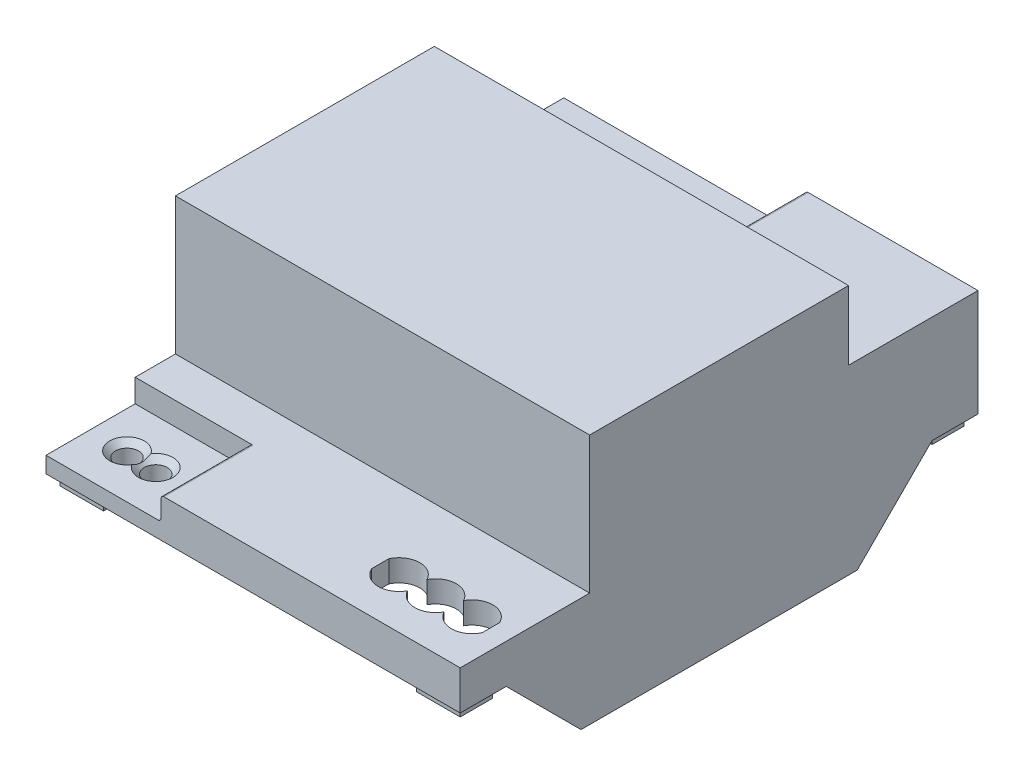
SolidWorks part; units mm, degrees
ref_plane "前视基准面" through (0, 0, 0) normal (0, 0, 1) x (1, 0, 0)
ref_plane "上视基准面" through (0, 0, 0) normal (0, 1, 0) x (1, 0, 0)
ref_plane "右视基准面" through (0, 0, 0) normal (1, 0, 0) x (0, 0, -1)
other "Configuration Table"
sketch "草图1" plane through (0, 0, 0) normal (0, 1, 0) x (1, 0, 0)
  line L1 (-36, 45) -> (36, 45)
  line L2 (-36, 45) -> (-36, -45)
  line L3 (-36, -45) -> (36, -45)
  line L4 (36, 45) -> (36, -45)
  dimension "D1" = 72
  dimension "D2" = 90
  dimension "D3" = 36
  dimension "D4" = 45
extrude "凸台-拉伸1" add sketch "草图1" along normal blind 43.6
sketch "草图2" plane through (36, 0, 0) normal (1, 0, 0) x (0, 0, -1)
  line L0 (-45, 0) -> (-45, 13)
  line L1 (-45, 43.6) -> (-45, 0) construction
  line L3 (-45, 0) -> (45, 0) construction
  line L4 (-24, 0) -> (-45, 0)
  line L5 (-45, 13) -> (-37, 13)
  line L6 (-37, 13) -> (-24, 0)
  dimension "D1" = 8
  dimension "D2" = 21
  dimension "D3" = 13
ref_plane "基准面1" through (0, 0, 0) normal (0, 0, -1) x (-1, 0, 0)
extrude "切除-拉伸1" cut sketch "草图2" against normal blind 72
mirror "镜向1" about plane through (0, 0, 0) normal (0, 0, -1) of "切除-拉伸1"
sketch "草图3" plane through (36, 0, 0) normal (1, 0, 0) x (0, 0, -1)
  line L0 (0, -16.83) -> (0, 16.83) construction
  line L1 (-45, 43.6) -> (-22.5, 43.6)
  line L2 (-45, 43.6) -> (-45, 19.8)
  line L3 (-45, 19.8) -> (-22.5, 19.8)
  line L4 (-22.5, 43.6) -> (-22.5, 19.8)
  line L5 (-37, 13) -> (-45, 13) construction
  dimension "D1" = 22.5
  dimension "D2" = 6.8
extrude "切除-拉伸2" cut sketch "草图3" against normal blind 72
sketch "草图5" plane through (0, 0, 0) normal (0, -1, 0) x (1, 0, 0)
  line L84 (-34, 20.5) -> (34, 20.5)
  line L85 (-10.23, 0) -> (10.23, 0) construction
  line L94 (34, 43) -> (-34, 43)
  line L95 (34, 37) -> (34, 43)
  line L96 (34, 24) -> (34, 37)
  line L97 (34, -24) -> (34, 24)
  line L98 (34, -37) -> (34, -24)
  line L99 (34, -43) -> (34, -37)
  line L100 (-34, -43) -> (34, -43)
  line L101 (-34, -37) -> (-34, -43)
  line L102 (-34, -24) -> (-34, -37)
  line L103 (-34, 43) -> (-34, 37)
  line L104 (-34, 37) -> (-34, 24)
  line L105 (-34, 24) -> (-34, -24)
  line L106 (34, 43) -> (-34, 43)
  line L107 (34, 37) -> (34, 43)
  line L108 (34, 20.5) -> (34, 37)
  line L115 (-34, 43) -> (-34, 37)
  line L116 (-34, 37) -> (-34, 20.5)
  dimension "D2" = 20.5
  dimension "D1" = 2
extrude "切除-拉伸4" cut sketch "草图5" against normal blind 16
sketch "草图6" plane through (0, 0, 0) normal (0, -1, 0) x (1, 0, 0)
  line L1 (-34, 20.5) -> (34, 20.5)
  line L2 (-34, 20.5) -> (-34, -20.5)
  line L3 (-34, -20.5) -> (34, -20.5)
  line L4 (34, 20.5) -> (34, -20.5)
  line L6 (-10.23, 0) -> (10.23, 0) construction
  line L7 (36, 24) -> (36, -24) construction
  line L8 (-36, -24) -> (-36, 24) construction
  dimension "D1" = 41
  dimension "D2" = 20.5
  dimension "D3" = 2
  dimension "D4" = 2
extrude "切除-拉伸5" cut sketch "草图6" against normal blind 42
sketch "草图7" plane through (0, 13, 0) normal (0, -1, 0) x (1, 0, 0)
  line L0 (-34, 38.2) -> (-34.8, 38.2)
  line L1 (-34, 43) -> (-34, 20.5) construction
  line L2 (-34.8, 38.2) -> (-34.8, 43.8)
  line L3 (-34.8, 43.8) -> (-27.2, 43.8)
  line L4 (-27.2, 43.8) -> (-27.2, 43)
  line L5 (-27.2, 43) -> (-34, 43)
  line L6 (-34, 43) -> (-34, 38.2)
  line L7 (-34, 43) -> (34, 43) construction
  line L8 (-36, 37) -> (-36, 45) construction
  line L9 (-36, 45) -> (36, 45) construction
  dimension "D1" = 1.2
  dimension "D2" = 1.2
  dimension "D3" = 4.8
  dimension "D4" = 6.8
extrude "凸台-拉伸2" add sketch "草图7" along normal blind 1.8
mirror "镜向4" about plane through (0, 0, 0) normal (1, 0, 0) of "凸台-拉伸2"
mirror "镜向5" about plane through (0, 0, 0) normal (0, 0, 1) of "镜向4"
sketch "草图8" plane through (0, 19.8, 0) normal (0, 1, 0) x (1, 0, 0)
  line L0 (36, -45) -> (36, -22.5) construction
  line L2 (32.62, -37.7748) -> (32.62, -34.7852)
  line L4 (13.37, -37.7748) -> (13.37, -34.7852)
  line L5 (-36, -45) -> (36, -45) construction
  arc A0 (13.37, -37.7748) -> (19.82, -37.9769) centre (16.645, -36.28) ccw
  arc A1 (19.82, -37.9769) -> (26.17, -37.9769) centre (22.995, -36.28) ccw
  arc A2 (32.62, -34.7852) -> (26.17, -34.5831) centre (29.345, -36.28) ccw
  arc A3 (19.82, -34.5831) -> (13.37, -34.7852) centre (16.645, -36.28) ccw
  arc A4 (26.17, -34.5831) -> (19.82, -34.5831) centre (22.995, -36.28) ccw
  arc A5 (26.17, -37.9769) -> (32.62, -37.7748) centre (29.345, -36.28) ccw
  dimension "D2" = 3.6
  dimension "D3" = 3.6
  dimension "D7" = 3.6
  dimension "D1" = 3.38
  dimension "D4" = 6.35
  dimension "D5" = 6.35
  dimension "D6" = 3.275
  dimension "D8" = 19.25
  dimension "D9" = 8.72
extrude "切除-拉伸6" cut sketch "草图8" against normal blind 3.8
sketch "草图10" plane through (0, 16, 0) normal (0, -1, 0) x (1, 0, 0)
  line L0 (34, 20.5) -> (-34, 20.5) construction
  line L1 (-34, 43) -> (-14, 43)
  line L2 (-34, 43) -> (-34, 20.5)
  line L3 (-34, 20.5) -> (-14, 20.5)
  line L4 (-14, 43) -> (-14, 20.5)
  dimension "D2" = 20
extrude "凸台-拉伸3" add sketch "草图10" along normal blind 4
sketch "草图9" plane through (-36, 0, 0) normal (-1, 0, 0) x (0, 0, 1)
  line L0 (45, 19.8) -> (22.5, 19.8) construction
  line L1 (45, 19.8) -> (29.5, 19.8)
  line L2 (45, 19.8) -> (45, 15.8)
  line L3 (45, 15.8) -> (29.5, 15.8)
  line L4 (29.5, 19.8) -> (29.5, 15.8)
  line L5 (45, 19.8) -> (45, 13) construction
  line L7 (22.5, 19.8) -> (22.5, 43.6) construction
  dimension "D1" = 7
  dimension "D2" = 4
extrude "切除-拉伸7" cut sketch "草图9" against normal blind 20
sketch "草图11" plane through (0, 15.8, 0) normal (0, 1, 0) x (1, 0, 0)
  line L0 (-36, -29.5) -> (-36, -45) construction
  line L1 (-16, -45) -> (-36, -45) construction
  circle A0 centre (-29.622, -37.3) radius 2
  circle A1 centre (-24.622, -37.3) radius 2
  dimension "D2" = 4
  dimension "D3" = 4
  dimension "D1" = 5
  dimension "D4" = 6.378
  dimension "D5" = 7.7
extrude "切除-拉伸8" cut sketch "草图11" against normal blind 4
chamfer "倒角1" distance 1 angle 45 2 edges at (-24.622, 15.8, 39.3) (-29.622, 15.8, 39.3)
sketch "草图13" plane through (0, 12, 0) normal (0, -1, 0) x (1, 0, 0)
  line L0 (-34, 24) -> (-34, 36) construction
  line L1 (-14, 20.5) -> (-34, 20.5)
  line L2 (-14, 20.5) -> (-14, 27.5)
  line L3 (-14, 27.5) -> (-34, 27.5)
  line L4 (-34, 20.5) -> (-34, 27.5)
  dimension "D1" = 7
extrude "切除-拉伸10" cut sketch "草图13" against normal blind 1.6
sketch "草图15" plane through (0, 16, 0) normal (0, -1, 0) x (1, 0, 0)
  line L0 (34, 20.5) -> (34, 43) construction
  line L1 (-14, 20.5) -> (34, 20.5)
  line L2 (-14, 20.5) -> (-14, 27.5)
  line L3 (-14, 27.5) -> (34, 27.5)
  line L4 (34, 20.5) -> (34, 27.5)
  line L5 (-14, 27.5) -> (-34, 27.5) construction
extrude "凸台-拉伸4" add sketch "草图15" along normal up to surface (2.4 mm away) up to face at (-24, 13.6, 24)
sketch "草图14" plane through (0, 13.6, 0) normal (0, -1, 0) x (1, 0, 0)
  line L0 (-36, -24) -> (-36, 24) construction
  line L1 (-14, 27.5) -> (-34, 27.5) construction
  line L3 (34, 27.5) -> (-14, 27.5) construction
  circle A0 centre (-26, 24) radius 1.75
  circle A2 centre (-6, 24) radius 1.75
  dimension "D1" = 3.5
  dimension "D5" = 3.5
  dimension "D2" = 10
  dimension "D3" = 3.5
  dimension "D4" = 20
  dimension "D6" = 3.5
extrude "切除-拉伸11" cut sketch "草图14" against normal blind 5
sketch "草图16" plane through (0, 0, 0) normal (0, -1, 0) x (1, 0, 0)
  line L1 (-34, -20.5) -> (34, -20.5)
  line L2 (-34, -20.5) -> (-34, -43)
  line L3 (-34, -43) -> (34, -43)
  line L4 (34, -20.5) -> (34, -43)
extrude "切除-拉伸12" cut sketch "草图16" against normal blind 30
sketch "草图18" plane through (0, 13.6, 0) normal (0, -1, 0) x (1, 0, 0)
  line L3 (5.8, 27.3) -> (5.8, 2)
  line L4 (15.8, -8) -> (33.8, -8)
  line L5 (-36, 45) -> (36, 45) construction
  line L22 (34, 27.3) -> (-14, 27.3)
  line L23 (-14, 27.3) -> (-34, 27.3)
  line L24 (5.8, 27.3) -> (-14, 27.3)
  line L25 (-14, 27.3) -> (-33.8, 27.3)
  line L34 (33.8, -24) -> (33.8, 24)
  line L35 (33.8, -42.8) -> (33.8, -8)
  line L37 (-33.8, 24) -> (-33.8, -24)
  line L38 (-33.8, 27.3) -> (-33.8, -42.8)
  line L40 (-34, -42.8) -> (34, -42.8)
  line L41 (-33.8, -42.8) -> (33.8, -42.8)
  arc A0 (5.8, 2) -> (15.8, -8) centre (15.8, 2) ccw
  dimension "D6" = 10
  dimension "D5" = 53
  dimension "D7" = 28
  dimension "D1" = 0.2
  dimension "D2" = 0.2
  dimension "D3" = 0.2
  dimension "D4" = 0.2
sketch "草图19" plane through (0, 0, -45) normal (0, 0, -1) x (-1, 0, 0)
  line L0 (24.25, 13.6) -> (27.75, 13.6) construction
  line L1 (-27, 27.6) -> (-11, 27.6)
  line L2 (-27, 27.6) -> (-27, 13.6)
  line L3 (-27, 13.6) -> (-11, 13.6)
  line L4 (-11, 27.6) -> (-11, 13.6)
  line L6 (-36, 43.6) -> (-36, 13) construction
  dimension "D1" = 16
  dimension "D2" = 14
  dimension "D3" = 9
extrude "切除-拉伸13" cut sketch "草图19" against normal blind 2
sketch "草图20" plane through (0, 30, 0) normal (0, -1, 0) x (1, 0, 0)
  line L0 (-34, -20.5) -> (-34, -43) construction
  line L3 (-34, -36.8) -> (-27.8, -36.8)
  line L4 (-27.8, -43) -> (-27.8, -36.8)
  line L7 (34, -36.8) -> (27.8, -36.8)
  line L8 (27.8, -43) -> (27.8, -36.8)
  line L9 (-34, -36.8) -> (-34, -43)
  line L10 (-34, -43) -> (-27.8, -43)
  line L11 (-27.2, -43) -> (27.2, -43) construction
  line L14 (34, -43) -> (34, -20.5) construction
  line L15 (34, -43) -> (27.2, -43) construction
  line L16 (-34, -38.2) -> (-34, -43) construction
  line L17 (-34, -43) -> (34, -43) construction
  line L18 (27.8, -43) -> (34, -43)
  line L19 (34, -38.2) -> (34, -43) construction
  line L20 (34, -43) -> (34, -36.8)
  line L21 (34, -37) -> (34, -24) construction
  circle A0 centre (-30.8, -39.8) radius 1.75
  circle A1 centre (30.8, -39.8) radius 1.75
  circle A2 centre (5, -39.8) radius 4
  circle A3 centre (5, -39.8) radius 1.75
  dimension "D5" = 3.5
  dimension "D6" = 3.5
  dimension "D4" = 3.5
  dimension "D9" = 8
  dimension "D2" = 6.2
  dimension "D3" = 6.2
  dimension "D7" = 6.2
  dimension "D8" = 6.2
  dimension "D10" = 5
  dimension "D11" = 30.8
  dimension "D12" = 39.8
  dimension "D13" = 30.8
  dimension "D14" = 39.8
  dimension "D15" = 39.8
extrude "凸台-拉伸5" add sketch "草图20" along normal up to surface (16.4 mm away) up to face at (-26, 13.6, 22.25)
sketch "草图21" plane through (0, 0, -45) normal (0, 0, -1) x (-1, 0, 0)
  line L0 (36, 43.6) -> (36, 13) construction
  line L1 (23.46, 17.5) -> (26.06, 17.5)
  line L2 (23.46, 17.5) -> (23.46, 14.5)
  line L3 (23.46, 14.5) -> (26.06, 14.5)
  line L4 (26.06, 17.5) -> (26.06, 14.5)
  line L5 (19.65, 17.5) -> (22.25, 17.5)
  line L6 (19.65, 17.5) -> (19.65, 14.5)
  line L7 (19.65, 14.5) -> (22.25, 14.5)
  line L8 (22.25, 17.5) -> (22.25, 14.5)
  line L9 (15.84, 17.5) -> (18.44, 17.5)
  line L10 (15.84, 17.5) -> (15.84, 14.5)
  line L11 (15.84, 14.5) -> (18.44, 14.5)
  line L12 (18.44, 17.5) -> (18.44, 14.5)
  line L13 (36, 13) -> (-36, 13) construction
  line L14 (8.46, 17.5) -> (11.06, 17.5)
  line L15 (8.46, 17.5) -> (8.46, 14.5)
  line L16 (8.46, 14.5) -> (11.06, 14.5)
  line L17 (11.06, 17.5) -> (11.06, 14.5)
  line L18 (4.65, 17.5) -> (7.25, 17.5)
  line L19 (4.65, 17.5) -> (4.65, 14.5)
  line L20 (4.65, 14.5) -> (7.25, 14.5)
  line L21 (7.25, 17.5) -> (7.25, 14.5)
  line L22 (0.84, 17.5) -> (3.44, 17.5)
  line L23 (0.84, 17.5) -> (0.84, 14.5)
  line L24 (0.84, 14.5) -> (3.44, 14.5)
  line L25 (3.44, 17.5) -> (3.44, 14.5)
  dimension "D1" = 2.6
  dimension "D2" = 3
  dimension "D3" = 2.6
  dimension "D4" = 2.6
  dimension "D5" = 1.21
  dimension "D6" = 1.21
  dimension "D7" = 9.94
  dimension "D8" = 1.5
  dimension "D9" = 2.6
  dimension "D10" = 3
  dimension "D11" = 2.6
  dimension "D12" = 2.6
  dimension "D13" = 1.21
  dimension "D14" = 1.21
  dimension "D15" = 4.78
extrude "切除-拉伸14" cut sketch "草图21" against normal blind 2
sketch "草图22" plane through (0, 30, 0) normal (0, -1, 0) x (1, 0, 0)
  circle A17 centre (30.8, -39.8) radius 1.75
  circle A18 centre (30.8, -39.8) radius 1.75
  circle A20 centre (5, -39.8) radius 1.75
  circle A21 centre (5, -39.8) radius 1.75
  circle A23 centre (-30.8, -39.8) radius 1.75
  circle A24 centre (-30.8, -39.8) radius 1.75
  dimension "D1" = 0
  dimension "D2" = 0
  dimension "D3" = 0
extrude "凸台-拉伸6" add sketch "草图22" along normal blind 11.4
sketch "草图24" plane through (0, 30, 0) normal (0, -1, 0) x (1, 0, 0)
  line L0 (-34, -20.5) -> (34, -20.5) construction
  line L1 (-34, -43) -> (9, -43)
  line L2 (-34, -43) -> (-34, -20.5)
  line L3 (-34, -20.5) -> (9, -20.5)
  line L4 (9, -43) -> (9, -20.5)
  arc A0 (7.4, -43) -> (2.6, -43) centre (5, -39.8) ccw construction
extrude "凸台-拉伸7" add sketch "草图24" along normal blind 7.5
chamfer "倒角3" distance 0.5 angle 45 24 edges at (-24.76, 14.5, -45) (-23.46, 16, -45) (-26.06, 16, -45) (-24.76, 17.5, -45) (-22.25, 16, -45) (-20.95, 17.5, -45) (-19.65, 16, -45) (-20.95, 14.5, -45) (-17.14, 14.5, -45) (-18.44, 16, -45) (-15.84, 16, -45) (-17.14, 17.5, -45) (-9.76, 14.5, -45) (-8.46, 16, -45) (-11.06, 16, -45) (-9.76, 17.5, -45) (-7.25, 16, -45) (-5.95, 14.5, -45) (-4.65, 16, -45) (-5.95, 17.5, -45) (-2.14, 14.5, -45) (-0.84, 16, -45) (-2.14, 17.5, -45) (-3.44, 16, -45)
sketch "草图28" plane through (36, 0, 0) normal (1, 0, 0) x (0, 0, -1)
  line L1 (45, 43.6) -> (22.5, 43.6)
  line L2 (45, 43.6) -> (45, 31.6)
  line L3 (45, 31.6) -> (22.5, 31.6)
  line L4 (22.5, 43.6) -> (22.5, 31.6)
  dimension "D1" = 22.5
  dimension "D2" = 12
extrude "切除-拉伸17" cut sketch "草图28" against normal blind 72
sketch "草图29" plane through (-36, 0, 0) normal (-1, 0, 0) x (0, 0, 1)
  line L0 (-22.5, 43.6) -> (-22.5, 31.6) construction
  line L1 (-45, 31.6) -> (-22.5, 31.6)
  line L2 (-45, 31.6) -> (-45, 24.6)
  line L3 (-45, 24.6) -> (-22.5, 24.6)
  line L4 (-22.5, 31.6) -> (-22.5, 24.6)
  dimension "D1" = 7
extrude "切除-拉伸18" cut sketch "草图29" against normal blind 42
sketch "草图30" plane through (0, 24.6, 0) normal (0, 1, 0) x (1, 0, 0)
  arc A0 (-22.905, 39.8591) -> (-22.905, 38.6409) centre (-24.81, 39.25) ccw
  arc A1 (-22.905, 38.6409) -> (-19.095, 38.6409) centre (-21, 39.25) ccw
  arc A2 (-19.095, 38.6409) -> (-19.095, 39.8591) centre (-17.19, 39.25) ccw
  arc A3 (-7.905, 39.8591) -> (-7.905, 38.6409) centre (-9.81, 39.25) ccw
  arc A6 (-7.905, 38.6409) -> (-4.095, 38.6409) centre (-6, 39.25) ccw
  arc A7 (-4.095, 38.6409) -> (-4.095, 39.8591) centre (-2.19, 39.25) ccw
  arc A8 (-19.095, 39.8591) -> (-22.905, 39.8591) centre (-21, 39.25) ccw
  arc A9 (-4.095, 39.8591) -> (-7.905, 39.8591) centre (-6, 39.25) ccw
  dimension "D1" = 4
  dimension "D2" = 4
  dimension "D4" = 39.25
  dimension "D3" = 7.38
  dimension "D5" = 2.19
extrude "切除-拉伸19" cut sketch "草图30" against normal blind 4
fillet "圆角3" radius 0.2 8 edges at (-7.905, 23.55, -38.6409) (-4.095, 23.55, -38.6409) (-4.095, 23.55, -39.8591) (-7.905, 23.55, -39.8591) (-19.095, 23.55, -38.6409) (-22.905, 23.55, -38.6409) (-22.905, 23.55, -39.8591) (-19.095, 23.55, -39.8591)
chamfer "倒角4" distance 0.2 angle 45 16 edges at (-0.19, 24.6, -39.25) (-4.095, 24.6, -40.1504) (-4.095, 24.6, -38.3496) (-6, 24.6, -41.25) (-6, 24.6, -37.25) (-7.905, 24.6, -40.1504) (-7.905, 24.6, -38.3496) (-11.81, 24.6, -39.25) (-22.905, 24.6, -38.3496) (-21, 24.6, -37.25) (-19.095, 24.6, -38.3496) (-15.19, 24.6, -39.25) (-19.095, 24.6, -40.1504) (-21, 24.6, -41.25) (-22.905, 24.6, -40.1504) (-26.81, 24.6, -39.25)
sketch "草图31" plane through (0, 13, 0) normal (0, -1, 0) x (1, 0, 0)
  line L0 (9, -43) -> (27.8, -43) construction
  line L1 (27.2, -43.8) -> (7.2, -43.8)
  line L2 (27.2, -43.8) -> (27.2, -43)
  line L3 (27.2, -43) -> (7.2, -43)
  line L4 (7.2, -43.8) -> (7.2, -43)
  dimension "D1" = 20
extrude "凸台-拉伸8" add sketch "草图31" along normal up to surface (1.8 mm away) up to face at (32, 11.2, -41.6667)
fillet "圆角4" radius 0.5 4 edges at (6, 24.6, -33.75) (6, 31.6, -33.75) (-16, 19.8, 37.25) (-16, 15.8, 37.25)
